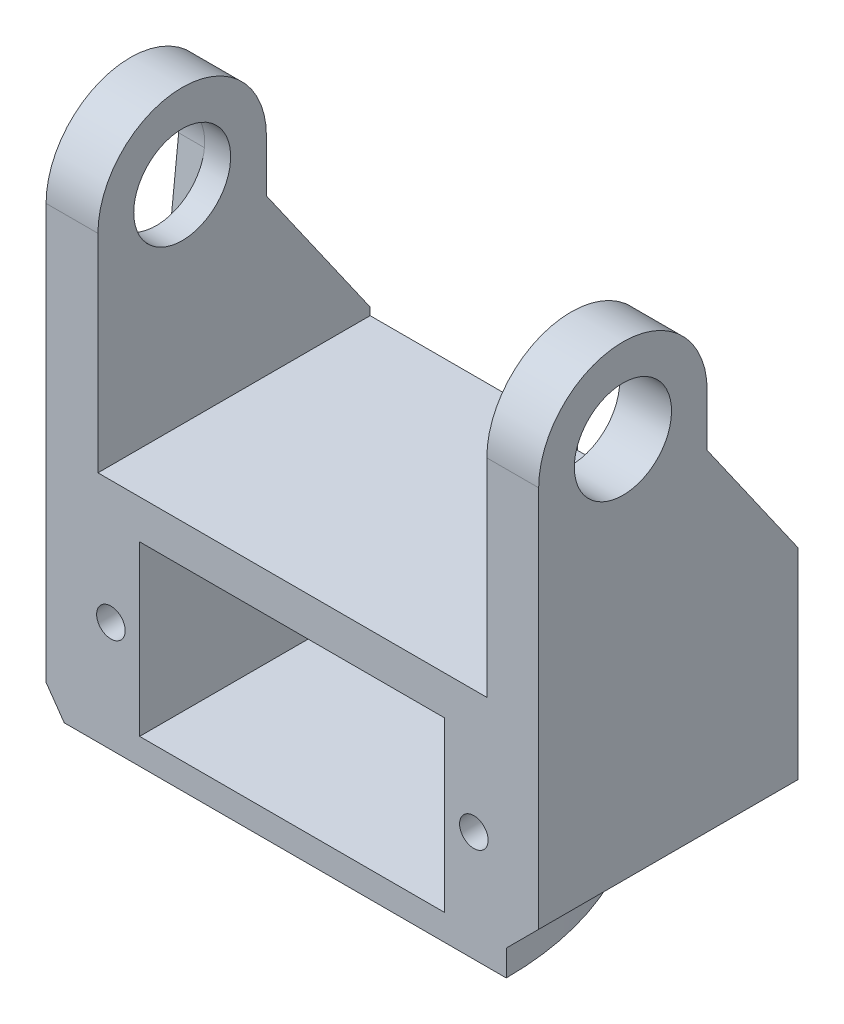
SolidWorks part; units mm, degrees
ref_plane "前视基准面" through (0, 0, 0) normal (0, 0, 1) x (1, 0, 0)
ref_plane "上视基准面" through (0, 0, 0) normal (0, 1, 0) x (1, 0, 0)
ref_plane "右视基准面" through (0, 0, 0) normal (1, 0, 0) x (0, 0, -1)
other "Configuration Table"
sketch "草图1" plane through (0, 0, 0) normal (0, 0, 1) x (1, 0, 0)
  line L0 (0, 22.1312) -> (0, 13) construction
  line L1 (-1013.0013, 0) -> (-11.7841, 0) construction
  line L2 (15, 16) -> (-15, 16)
  line L3 (-15, 16) -> (-15, 32)
  line L4 (-15, 32) -> (-19, 32)
  line L5 (-19, 32) -> (-19, 0)
  line L6 (-19, 0) -> (-11.7841, 0)
  line L7 (19, 32) -> (19, 0)
  line L8 (15, 32) -> (19, 32)
  line L9 (15, 16) -> (15, 32)
  line L10 (11.75, 0) -> (19, 0)
  line L12 (-11.7841, 0) -> (-11.7841, 13)
  line L13 (-11.7841, 13) -> (11.75, 13)
  line L14 (11.75, 0) -> (11.75, 13)
  line L17 (11.75, 0) -> (1015.2021, 0) construction
  circle A0 centre (-14, 6.5) radius 1.1
  circle A1 centre (14, 6.5) radius 1.1
  point P3 (0, 0)
  point P12 (0, 0)
  point P15 (0, 16)
  point P19 (-15.3921, 0)
  dimension "D4" = 28
  dimension "D5" = 6.5
  dimension "D8" = 2.2
  dimension "D1" = 16
  dimension "D2" = 4
  dimension "D3" = 13
  dimension "D6" = 32
  dimension "D7" = 30
extrude "凸台-拉伸1" add sketch "草图1" along normal blind 13
sketch "草图2" plane through (19, 0, 0) normal (1, 0, 0) x (0, 0, -1)
  line L0 (-13, 32) -> (0, 32) construction
  line L1 (0, 0) -> (0, 32) construction
  line L2 (0, 32) -> (-13, 32)
  arc A0 (-13, 32) -> (0, 32) centre (-6.5, 32) cw
extrude "凸台-拉伸2" add sketch "草图2" against normal blind 4
mirror "镜向1" about plane through (0, 0, 0) normal (1, 0, 0) of "凸台-拉伸2"
sketch "草图3" plane through (-19, 0, 0) normal (-1, 0, 0) x (0, 0, 1)
  line L0 (2.7712, 31.6023) -> (4.5113, 15.2879)
  line L1 (10.2288, 31.6023) -> (8.4887, 15.2879)
  line L2 (6.5, 42.5543) -> (6.5, 10.465) construction
  arc A0 (10.2288, 31.6023) -> (2.7712, 31.6023) centre (6.5, 32) ccw
  arc A1 (4.5113, 15.2879) -> (8.4887, 15.2879) centre (6.5, 15.5) ccw
  point P6 (6.9193, 13.3438)
  dimension "D1" = 7.5
  dimension "D3" = 4
  dimension "D2" = 16.5
extrude "切除-拉伸1" cut sketch "草图3" against normal blind 2
sketch "草图4" plane through (-17, 0, 0) normal (-1, 0, 0) x (0, 0, 1)
  circle A0 centre (6.5, 32) radius 3.7382
extrude "切除-拉伸2" cut sketch "草图4" against normal blind 2
sketch "草图5" plane through (0, 0, 0) normal (0, 0, -1) x (-1, 0, 0)
  line L0 (-19, 16) -> (19, 16)
  line L1 (-19, 0) -> (-19, 32) construction
  line L2 (19, 32) -> (19, 0) construction
  line L3 (19, 16) -> (19, 0)
  line L4 (19, 0) -> (16.5, 0)
  line L5 (19, 0) -> (11.7841, 0) construction
  line L6 (16.5, 0) -> (16.5, 14)
  line L7 (16.5, 14) -> (-16.5, 14)
  line L8 (-16.5, 14) -> (-16.5, 0)
  line L9 (-11.75, 0) -> (-19, 0) construction
  line L10 (-16.5, 0) -> (-19, 0)
  line L11 (-19, 0) -> (-19, 16)
  line L12 (-15, 16) -> (15, 16) construction
  dimension "D1" = 33
  dimension "D2" = 2
extrude "凸台-拉伸4" add sketch "草图5" along normal blind 7
sketch "草图9" plane through (19, 0, 0) normal (1, 0, 0) x (0, 0, -1)
  circle A0 centre (-6.5, 32) radius 3.75
  dimension "D1" = 7.5
extrude "切除-拉伸3" cut sketch "草图9" against normal blind 10
sketch "草图10" plane through (0, 0, -7) normal (0, 0, -1) x (-1, 0, 0)
  line L0 (19, 16) -> (-19, 16) construction
  line L1 (19, 0) -> (-1, 0)
  line L2 (19, 0) -> (19, 16)
  line L3 (19, 16) -> (-1, 16)
  line L4 (-1, 0) -> (-1, 16)
  dimension "D1" = 20
extrude "凸台-拉伸5" add sketch "草图10" along normal blind 2.25
sketch "草图11" plane through (0, 0, -7) normal (0, 0, 1) x (1, 0, 0)
  circle A0 centre (-14, 6.5) radius 1.1 construction
  circle A1 centre (-5, 6.5) radius 3.6
  dimension "D2" = 7.2
  dimension "D1" = 9
chamfer "倒角1" distance 2.5 angle 45 1 edges at (19, 0, 3)
sketch "草图12" plane through (0, 0, 0) normal (0, -1, 0) x (1, 0, 0)
  line L0 (1, 13) -> (16.5, 13)
  line L1 (-19, 13) -> (1, 13)
  line L2 (-19, 13) -> (-19, -9.25)
  line L3 (-19, -9.25) -> (1, -9.25)
  arc A0 (1, -9.25) -> (16.5, 13) centre (-7.2266, 13.0048) ccw
extrude "凸台-拉伸8" add sketch "草图12" along normal blind 2
sketch "草图13" plane through (0, 0, -9.25) normal (0, 0, -1) x (-1, 0, 0)
  line L5 (19, -2) -> (19, 16)
  line L6 (19, 16) -> (-1, 16)
  line L7 (-1, 16) -> (-1, 0)
  line L8 (-1, 0) -> (-1, -2)
  line L9 (-1, -2) -> (19, -2)
  line L10 (19, -2) -> (19, 16)
  line L11 (19, 16) -> (-1, 16)
  line L12 (-1, 16) -> (-1, 0)
  line L13 (-1, 0) -> (-1, -2)
  line L14 (-1, -2) -> (19, -2)
  dimension "D1" = 0
extrude "切除-拉伸4" cut sketch "草图13" against normal blind 1.25
extrude "凸台-拉伸9" add sketch "草图11" against normal blind 5.25
sketch "草图15" plane through (0, 0, -7) normal (0, 0, 1) x (1, 0, 0)
  line L4 (1, 0) -> (1, 14)
  line L5 (1, 14) -> (-16.5, 14)
  line L6 (-16.5, 14) -> (-16.5, 0)
  line L7 (-16.5, 0) -> (1, 0)
  line L8 (1, 0) -> (1, 14)
  line L9 (1, 14) -> (-16.5, 14)
  line L10 (-16.5, 14) -> (-16.5, 0)
  line L11 (-16.5, 0) -> (1, 0)
  dimension "D1" = 0
extrude "凸台-拉伸10" add sketch "草图15" along normal blind 1.25
chamfer "倒角2" distance 12 angle 35 1 edges at (-17, 16, 0) first distance on face at (-17, 24, 0)
chamfer "倒角3" distance 12 angle 35 1 edges at (17, 16, 0) first distance on face at (17, 24, 0)
chamfer "倒角4" distance 2 angle 35 1 edges at (-19, -2, 2.5) first distance on face at (-19, 24.035, 6.5)
